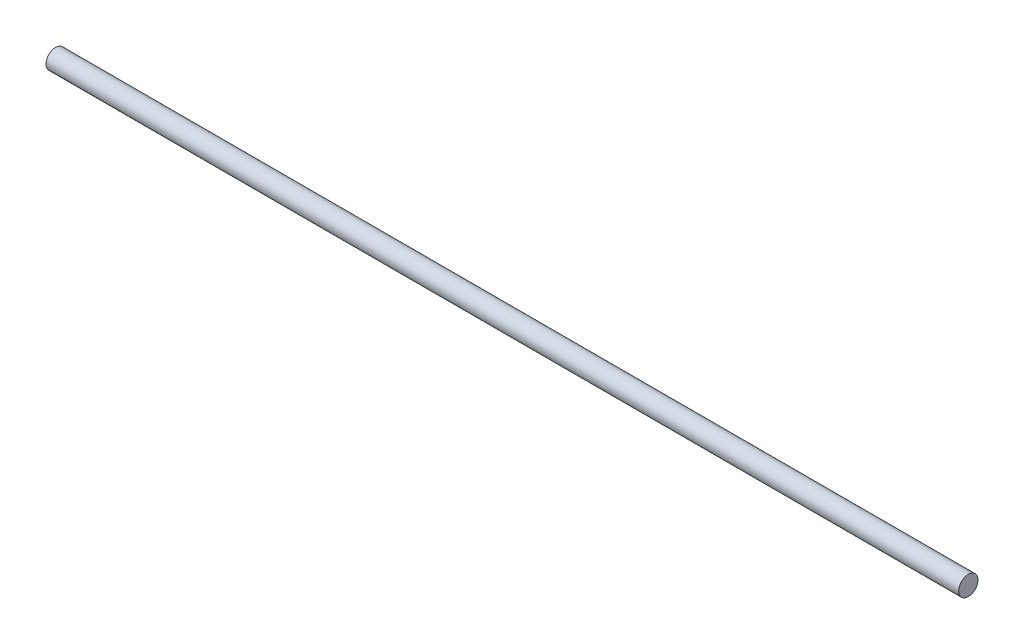
SolidWorks part; units mm, degrees
ref_plane "Front Plane" through (0, 0, 0) normal (0, 0, 1) x (1, 0, 0)
ref_plane "Top Plane" through (0, 0, 0) normal (0, 1, 0) x (1, 0, 0)
ref_plane "Right Plane" through (0, 0, 0) normal (1, 0, 0) x (0, 0, -1)
sketch "Sketch1" plane through (0, 0, 0) normal (1, 0, 0) x (0, 0, -1)
  circle A0 centre (0, 0) radius 4.5
  dimension "D1" = 9
extrude "Boss-Extrude1" add sketch "Sketch1" along normal blind 425
